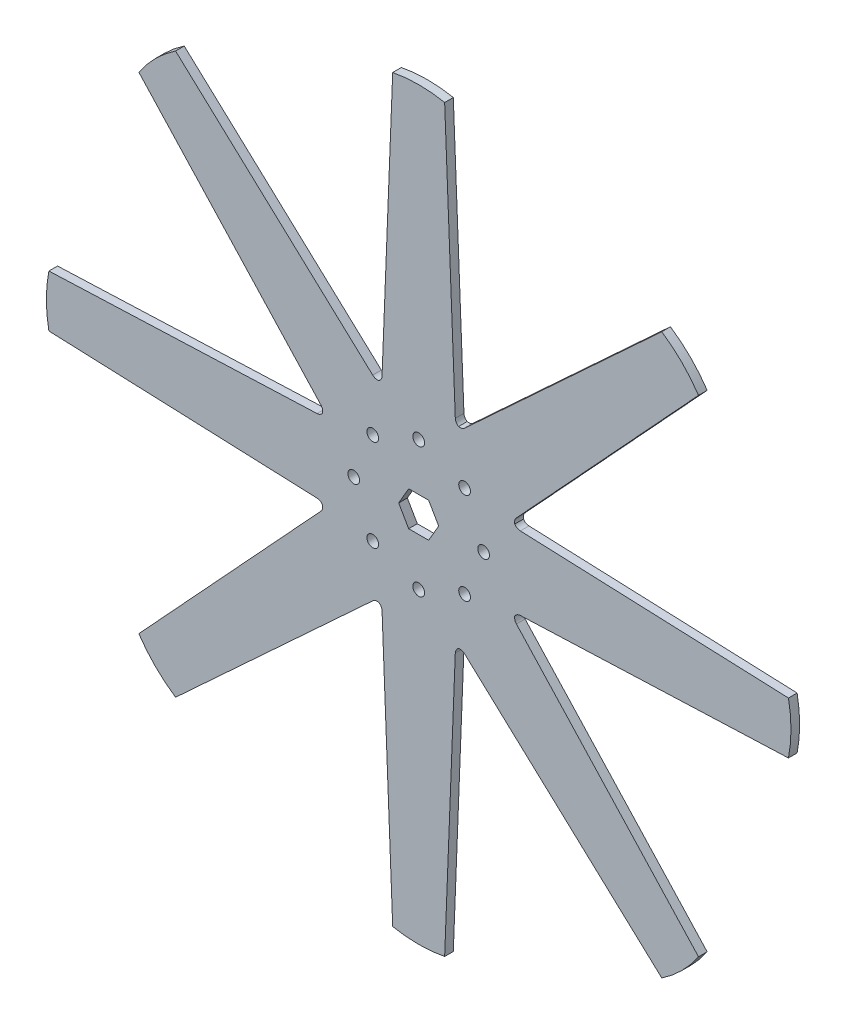
SolidWorks part; units mm, degrees
ref_plane "Front Plane" through (0, 0, 0) normal (0, 0, 1) x (1, 0, 0)
ref_plane "Top Plane" through (0, 0, 0) normal (0, 1, 0) x (1, 0, 0)
ref_plane "Right Plane" through (0, 0, 0) normal (1, 0, 0) x (0, 0, -1)
sketch "Sketch1" plane through (0, 0, 0) normal (0, 0, 1) x (1, 0, 0)
  circle A0 centre (0, 0) radius 38.1
  dimension "D1" = 76.2
extrude "Boss-Extrude1" add sketch "Sketch1" along normal blind 3.175
sketch "Sketch2" plane through (0, 0, 3.175) normal (0, 0, 1) x (1, 0, 0)
  line L0 (0, 38.1) -> (0, 136.525) construction
  line L1 (-13.4937, 35.6304) -> (-9.525, 135.5944)
  line L2 (13.4937, 35.6304) -> (9.525, 135.5944)
  circle A0 centre (0, 0) radius 38.1 construction
  arc A1 (-9.525, 135.5944) -> (9.525, 135.5944) centre (0, 87.3125) cw
  arc A2 (-13.4937, 35.6304) -> (13.4937, 35.6304) centre (0, 0) cw
  dimension "D1" = 98.425
  dimension "D2" = 19.05
  dimension "D3" = 26.9875
extrude "Boss-Extrude2" add sketch "Sketch2" against normal blind 3.175
pattern_circular "CirPattern1" count 8 over 360 about axis through (0, 0, 3.175) along (0, 0, 1) of "Boss-Extrude2"
sketch "Sketch3" plane through (0, 0, 3.175) normal (0, 0, 1) x (1, 0, 0)
  line L0 (0, 56.7704) -> (0, -85.6367) construction
  line L2 (3.6662, 6.35) -> (-3.6662, 6.35)
  line L3 (-3.6662, 6.35) -> (-7.3323, 0)
  line L4 (-7.3323, 0) -> (-3.6662, -6.35)
  line L5 (-3.6662, -6.35) -> (3.6662, -6.35)
  line L6 (3.6662, -6.35) -> (7.3323, 0)
  line L7 (7.3323, 0) -> (3.6662, 6.35)
  circle A0 centre (0, 0) radius 6.35 construction
  dimension "D1" = 12.7
extrude "Cut-Extrude1" cut sketch "Sketch3" against normal blind 3.175
sketch "Sketch4" plane through (0, 0, 3.175) normal (0, 0, 1) x (1, 0, 0)
  line L0 (0, 10.6802) -> (0, 57.6793) construction
  circle A0 centre (0, 23.8125) radius 2.1501
  dimension "D1" = 4.3002
  dimension "D2" = 23.8125
extrude "Cut-Extrude2" cut sketch "Sketch4" against normal blind 3.175
pattern_circular "CirPattern2" count 8 over 360 about axis through (0, 0, 3.175) along (0, 0, 1) of "Cut-Extrude2"
fillet "Fillet1" radius 2.54 16 edges at (35.6304, 13.4938, 1.5875) (34.7361, 15.653, 1.5875) (15.653, 34.7361, 1.5875) (13.4938, 35.6304, 1.5875) (-13.4938, 35.6304, 1.5875) (-15.653, 34.7361, 1.5875) (-34.7361, 15.653, 1.5875) (-35.6304, 13.4937, 1.5875) (-35.6304, -13.4938, 1.5875) (-34.7361, -15.653, 1.5875) (-15.653, -34.7361, 1.5875) (-13.4938, -35.6304, 1.5875) (13.4938, -35.6304, 1.5875) (15.653, -34.7361, 1.5875) (34.7361, -15.653, 1.5875) (35.6304, -13.4937, 1.5875)
